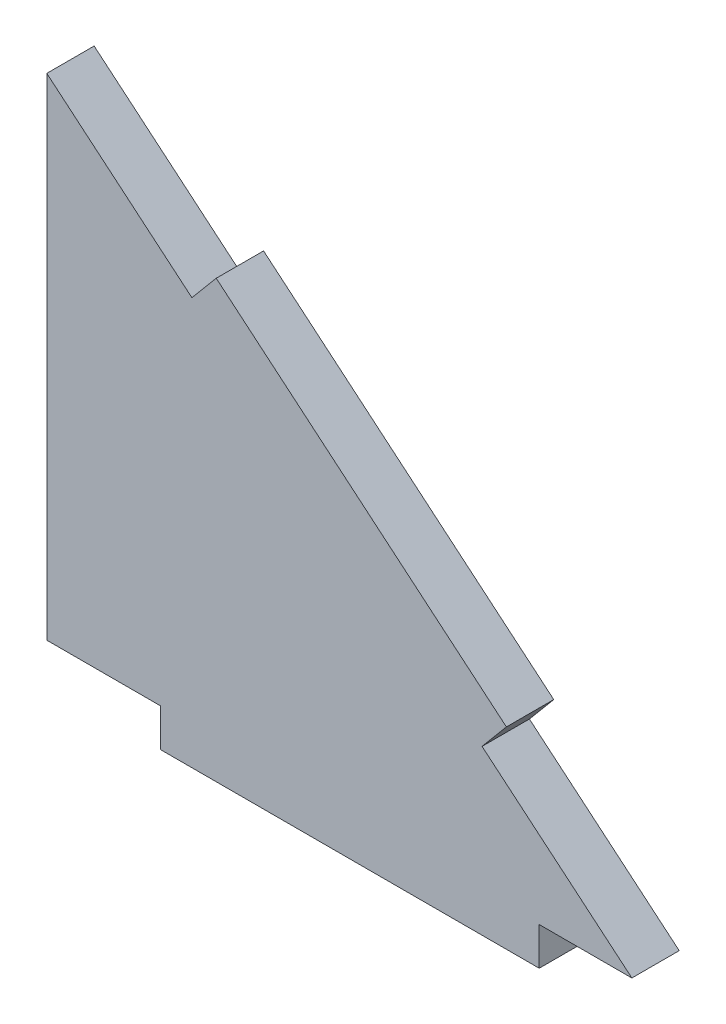
SolidWorks part; units mm, degrees
ref_plane "前视基准面" through (0, 0, 0) normal (0, 0, 1) x (1, 0, 0)
ref_plane "上视基准面" through (0, 0, 0) normal (0, 1, 0) x (1, 0, 0)
ref_plane "右视基准面" through (0, 0, 0) normal (1, 0, 0) x (0, 0, -1)
other "Configuration Table"
sketch "草图1" plane through (0, 0, 0) normal (0, 0, 1) x (1, 0, 0)
  line L2 (-23.0204, 5.056) -> (-23.0204, 9.056)
  line L3 (16.9796, 5.056) -> (16.9796, 9.056)
  line L4 (-23.0204, 9.056) -> (-35.0204, 9.056)
  line L6 (-35.0204, 9.056) -> (-35.0204, 60.8969)
  line L7 (-35.0204, 60.8969) -> (-19.6995, 48.0411)
  line L10 (-19.6995, 48.0411) -> (-17.1284, 51.1053)
  line L11 (-17.1284, 51.1053) -> (13.5134, 25.3938)
  line L12 (13.5134, 25.3938) -> (10.9422, 22.3296)
  line L15 (-23.0204, 5.056) -> (16.9796, 5.056)
  line L16 (24.8387, 10.6691) -> (10.9422, 22.3296)
  line L17 (24.8387, 10.6691) -> (25.7025, 9.9442)
  line L19 (16.9796, 9.056) -> (26.7611, 9.056)
  line L20 (26.7611, 9.056) -> (25.7025, 9.9442)
  point P4 (0, 0)
  dimension "D1" = 40
  dimension "D3" = 12
  dimension "D4" = 90
  dimension "D5" = 40
  dimension "D6" = 4
  dimension "D7" = 4
  dimension "D8" = 90
  dimension "D9" = 20.65
  dimension "D10" = 90
  dimension "D11" = 90
  dimension "D12" = 90
  dimension "D13" = 90
  dimension "D14" = 4
  dimension "D15" = 40
  dimension "D16" = 4
  dimension "D17" = 90
  dimension "D18" = 90
  dimension "D19" = 20
  dimension "D20" = 90
  dimension "D21" = 40
  dimension "D22" = 9.7815
extrude "凸台-拉伸1" add sketch "草图1" along normal blind 5
